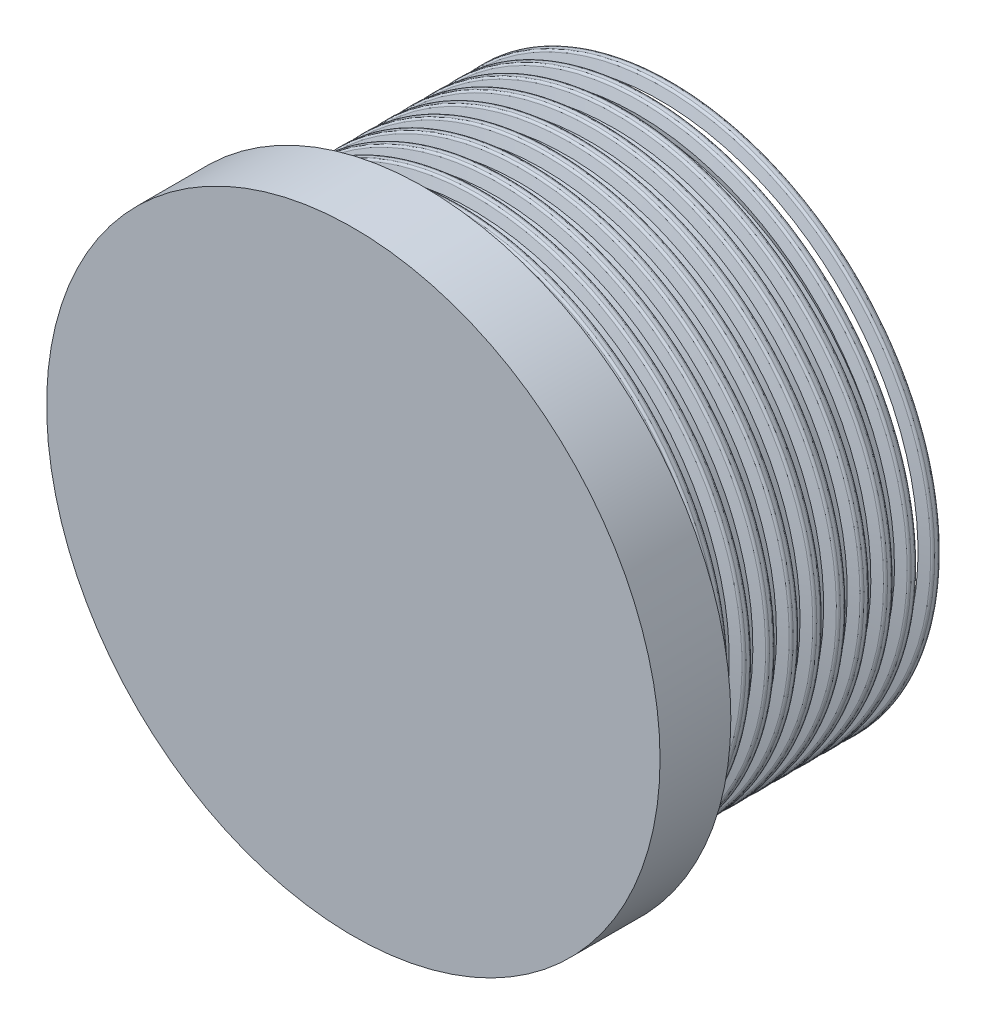
SolidWorks part; units mm, degrees
ref_plane "Plan de face" through (0, 0, 0) normal (0, 0, 1) x (1, 0, 0)
ref_plane "Plan de dessus" through (0, 0, 0) normal (0, 1, 0) x (1, 0, 0)
ref_plane "Plan de droite" through (0, 0, 0) normal (1, 0, 0) x (0, 0, -1)
sketch "Esquisse1" plane through (0, 0, 0) normal (1, 0, 0) x (0, 0, -1)
  line L0 (-6.5, 0) -> (6.5, 0) construction
  line L1 (-6.5, 0) -> (-6.5, 13)
  line L2 (-6.5, 13) -> (-3.5, 13)
  line L3 (-3.5, 13) -> (-3.5, 11)
  line L4 (-3.5, 11) -> (6.5, 11)
  line L5 (6.5, 11) -> (6.5, 9)
  line L6 (6.5, 9) -> (-3.5, 9)
  line L7 (-3.5, 9) -> (-3.5, 0)
  line L8 (-6.5, 0) -> (-3.5, 0)
  dimension "D1" = 13
  dimension "D2" = 3
  dimension "D3" = 11
  dimension "D4" = 2
  dimension "D5" = 10
revolve "Révolution1" add sketch "Esquisse1" angle 360 about L0
chamfer "Chanfrein1" distance 1 angle 30 1 edges at (11, 0, -6.5) first distance on face at (11, 0, 3.5)
thread "Filetage1" [suppressed] pitch 1.5 start angle 0, offset 2, length 0, pitch 1.5, diameter 21.8
ref_plane "Plan2" through (10.9, 0, -8.5) normal (0, -1, 0) x (1, 0, 0)
sketch "Profil de filetage2" plane through (10.9, 0, -8.5) normal (0, -1, 0) x (1, 0, 0)
  line L0 (0, 0) -> (0, 1.5) construction
  line L1 (0, 0) -> (0.8119, 0.4687)
  line L2 (0.8119, 0.4687) -> (0.8119, 0.6562)
  line L3 (0.8119, 0.6562) -> (0, 1.125)
  line L4 (0.8119, 0.5625) -> (0, 0.5625) construction
  line L11 (0, 0) -> (0, 1.125)
  point P2 (0, 0)
  dimension "Pitch" = 1.5
  dimension "Profile_Angle" = 60
  dimension "Profile_Land" = 0.1875
  dimension "Profile_Height" = 0.8119
sketch "Esquisse5" plane through (0, 0, 0) normal (1, 0, 0) x (0, 0, -1)
  line L0 (-4.3179, 11) -> (-4.2038, 11.4259)
  line L1 (-4.1072, 11.5) -> (-3.9607, 11.5)
  line L2 (-3.8641, 11.4259) -> (-3.75, 11)
  line L3 (5.5, 11) -> (-3.5, 11) construction
  line L4 (-4.034, 11.5) -> (-4.034, 11) construction
  line L5 (-4.3179, 11) -> (-3.75, 11)
  line L6 (-4.3179, 11) -> (-4.5679, 11) construction
  line L7 (-3.75, 11) -> (-3.5, 11) construction
  line L8 (-3.5, -13) -> (-3.5, 13) construction
  line L9 (-4.5679, 11) -> (-4.5679, 11.5) construction
  arc A0 (-4.2038, 11.4259) -> (-4.1072, 11.5) centre (-4.1072, 11.4) cw
  arc A1 (-3.9607, 11.5) -> (-3.8641, 11.4259) centre (-3.9607, 11.4) cw
  point P26 (-4.184, 11.5)
  point P29 (-3.884, 11.5)
  dimension "D5" = 0.1
  dimension "D1" = 15
  dimension "D2" = 11.5
  dimension "D3" = 0.3
  dimension "D4" = 0.25
ref_plane "Plan3" through (0, 0, 4.034) normal (0, 0, -1) x (-1, 0, 0)
sketch "Esquisse7" plane through (0, 0, 4.034) normal (0, 0, -1) x (-1, 0, 0)
  circle A0 centre (0, 0) radius 11
  circle A1 centre (0, 0) radius 11 construction
curve "Hélice/Spirale1" pitch 1 height 11.25 turns 11.25
sweep "Balayage1" add profiles "Esquisse5" path "Hélice/Spirale1"
chamfer "Chanfrein2" [suppressed] distance 3 angle 10
fillet "Congé4" [suppressed] radius 0.1
